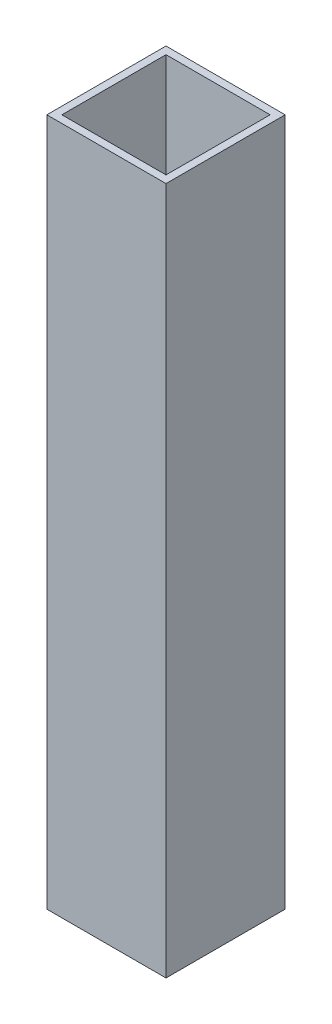
SolidWorks part; units mm, degrees
ref_plane "Front Plane" through (0, 0, 0) normal (0, 0, 1) x (1, 0, 0)
ref_plane "Top Plane" through (0, 0, 0) normal (0, 1, 0) x (1, 0, 0)
ref_plane "Right Plane" through (0, 0, 0) normal (1, 0, 0) x (0, 0, -1)
sketch "Sketch1" plane through (0, 0, 0) normal (0, 1, 0) x (1, 0, 0)
  line L1 (-9.525, -9.525) -> (9.525, -9.525)
  line L2 (-9.525, -9.525) -> (-9.525, 9.525)
  line L3 (-9.525, 9.525) -> (9.525, 9.525)
  line L4 (9.525, -9.525) -> (9.525, 9.525)
  line L5 (-9.525, -9.525) -> (9.525, 9.525) construction
  line L6 (-9.525, 9.525) -> (9.525, -9.525) construction
  point P0 (0, 0)
  dimension "D1" = 19.05
sketch "Sketch2" plane through (0, 0, 0) normal (0, 1, 0) x (1, 0, 0)
  line L14 (8.325, -8.325) -> (8.325, 8.325)
  line L15 (-8.325, -8.325) -> (8.325, -8.325)
  line L16 (-8.325, 8.325) -> (-8.325, -8.325)
  line L17 (8.325, 8.325) -> (-8.325, 8.325)
  line L18 (8.325, -8.325) -> (8.325, 8.325)
  line L19 (-8.325, -8.325) -> (8.325, -8.325)
  line L20 (-8.325, 8.325) -> (-8.325, -8.325)
  line L21 (8.325, 8.325) -> (-8.325, 8.325)
  dimension "D1" = 1.2
extrude "Boss-Extrude1" add sketch "Sketch1" along normal blind 110
extrude "Cut-Extrude3" cut sketch "Sketch2" along normal through all
